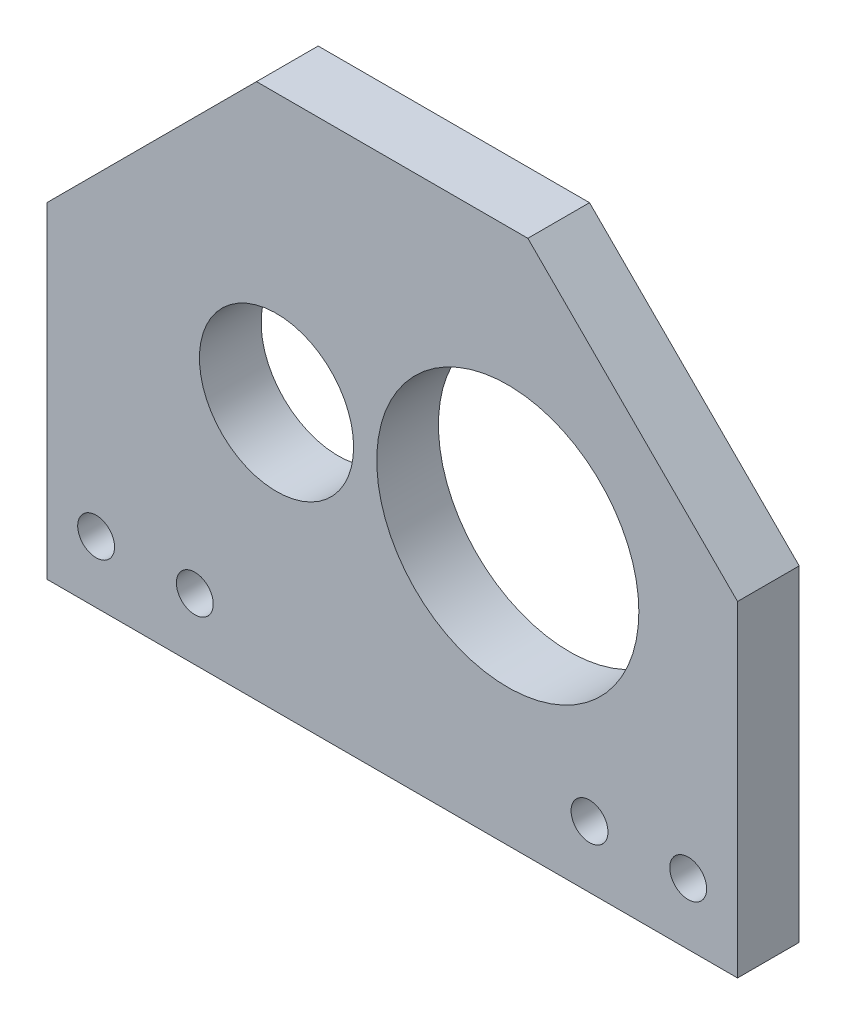
SolidWorks part; units mm, degrees
ref_plane "Front Plane" through (0, 0, 0) normal (0, 0, 1) x (1, 0, 0)
ref_plane "Top Plane" through (0, 0, 0) normal (0, 1, 0) x (1, 0, 0)
ref_plane "Right Plane" through (0, 0, 0) normal (1, 0, 0) x (0, 0, -1)
sketch "Sketch1" plane through (0, 0, 0) normal (0, 0, 1) x (1, 0, 0)
  line L1 (35.56, -27.5819) -> (-35.56, -27.5819)
  line L2 (35.56, -27.5819) -> (35.56, 27.5819)
  line L3 (35.56, 27.5819) -> (-35.56, 27.5819)
  line L4 (-35.56, -27.5819) -> (-35.56, 27.5819)
  line L5 (35.56, -27.5819) -> (-35.56, 27.5819) construction
  line L6 (35.56, 27.5819) -> (-35.56, -27.5819) construction
  circle A0 centre (11.9062, 0) radius 13.4937
  circle A1 centre (-11.9062, 0) radius 7.9375
  point P0 (0, 0)
  dimension "D3" = 26.9875
  dimension "D6" = 15.875
  dimension "D1" = 71.12
  dimension "D2" = 55.1637
  dimension "D4" = 0
  dimension "D5" = 0
  dimension "D7" = 11.9062
  dimension "D8" = 11.9062
extrude "Boss-Extrude1" add sketch "Sketch1" along normal blind 6.35
hole_wizard "#6 Clearance Hole1" positions "Sketch2" profile "Sketch3" hole size "#6" standard "ANSI Inch" end condition through all
sketch "Sketch2" plane through (0, 0, 6.35) normal (0, 0, 1) x (1, 0, 0)
  line L1 (-30.48, -21.2319) -> (-20.32, -21.2319)
  line L3 (20.32, -21.2319) -> (30.48, -21.2319)
  line L5 (-35.56, -27.5819) -> (35.56, -27.5819) construction
  line L6 (-35.56, 27.5819) -> (-35.56, -27.5819) construction
  line L7 (35.56, -27.5819) -> (35.56, 27.5819) construction
  point P0 (-30.48, -21.2319)
  point P2 (-20.32, -21.2319)
  point P4 (20.32, -21.2319)
  point P6 (30.48, -21.2319)
  dimension "D1" = 10.16
  dimension "D2" = 10.16
  dimension "D3" = 6.35
  dimension "D4" = 6.35
  dimension "D5" = 5.08
  dimension "D6" = 5.08
sketch "Sketch3" plane through (-30.48, -21.2319, 6.35) normal (1, 0, 0) x (0, -1, 0)
  line L0 (0, 0) -> (0, 6.35)
  line L1 (0, 6.35) -> (1.8986, 6.35)
  line L2 (1.8986, 6.35) -> (1.8986, 0)
  line L5 (1.8986, 0) -> (0, 0)
  line L11 (0, -6.35) -> (0, 107.95) construction
  dimension "Thru Hole Dia." = 3.7973
  dimension "Thru Hole Depth" = 6.35
sketch "Sketch4" plane through (0, 0, 6.35) normal (0, 0, 1) x (1, 0, 0)
  line L0 (-35.56, 5.9919) -> (-13.97, 27.5819)
  line L1 (-35.56, 27.5819) -> (-35.56, -27.5819) construction
  line L2 (35.56, 27.5819) -> (-35.56, 27.5819) construction
  line L3 (35.56, 5.9919) -> (13.97, 27.5819)
  line L4 (35.56, -27.5819) -> (35.56, 27.5819) construction
  line L5 (-35.56, 27.5819) -> (-35.56, 5.9919)
  line L6 (-13.97, 27.5819) -> (-35.56, 27.5819)
  line L7 (13.97, 27.5819) -> (35.56, 27.5819)
  line L8 (35.56, 27.5819) -> (35.56, 5.9919)
  dimension "D1" = 21.59
  dimension "D2" = 21.59
  dimension "D3" = 21.59
  dimension "D4" = 21.59
extrude "Cut-Extrude1" cut sketch "Sketch4" against normal through all
